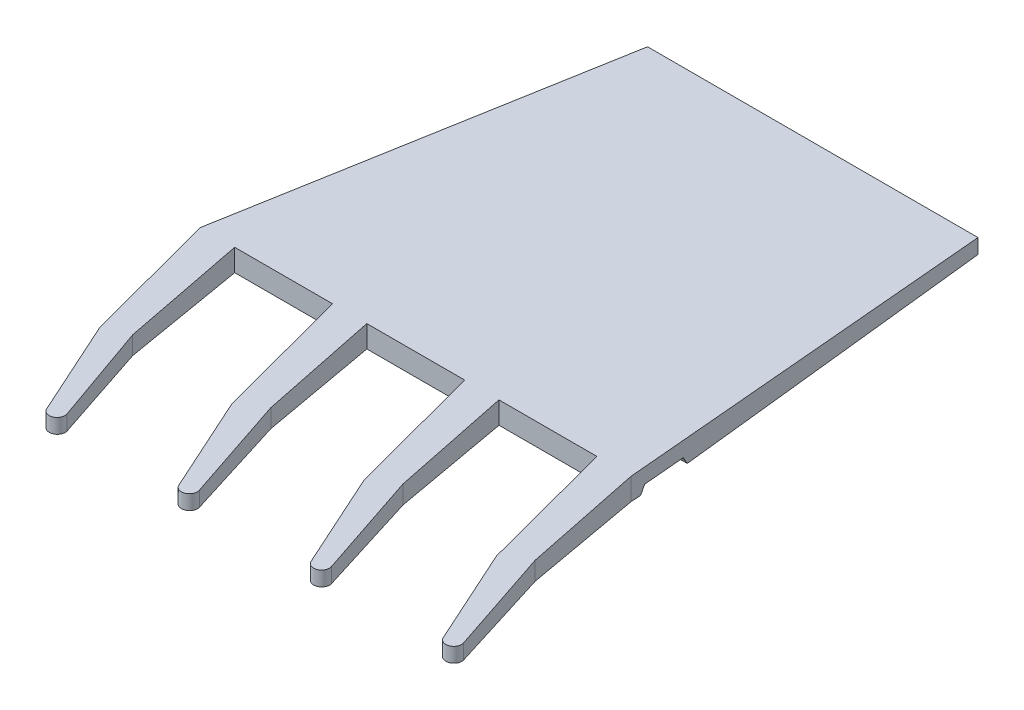
SolidWorks part; units mm, degrees
ref_plane "Front Plane" through (0, 0, 0) normal (0, 0, 1) x (1, 0, 0)
ref_plane "Top Plane" through (0, 0, 0) normal (0, 1, 0) x (1, 0, 0)
ref_plane "Right Plane" through (0, 0, 0) normal (1, 0, 0) x (0, 0, -1)
sketch "Sketch1" plane through (0, 0, 0) normal (0, 1, 0) x (1, 0, 0)
  line L0 (-32.5781, 0) -> (72.7976, 0) construction
  line L5 (0, 0) -> (0, 68.3726) construction
  line L27 (72.7976, -27.2489) -> (65.0609, -10.928) construction
  line L30 (-32.5781, 8.3167) -> (-32.5781, -27.2489) construction
  line L54 (-28, 8.3167) -> (-32.5781, 8.3167) construction
  line L60 (0, 68.3726) -> (0, -57.1527) construction
  line L62 (-32.5781, 68.3726) -> (72.7976, 68.3726) construction
  line L63 (-32.5781, 68.3726) -> (-32.5781, -57.1527) construction
  line L64 (-32.5781, -57.1527) -> (72.7976, -57.1527) construction
  line L65 (72.7976, 68.3726) -> (72.7976, -57.1527) construction
sketch "Sketch2" plane through (0, 0, 0) normal (1, 0, 0) x (0, 0, -1)
  line L0 (3.2707, -4.5742) -> (68.4088, -3.0014) construction
  line L1 (68.3726, 0) -> (68.4088, -3.0014) construction
  line L2 (68.3726, 0) -> (-57.1527, 0) construction
  line L7 (-7.1582, -4.5614) -> (-57.1563, -3) construction
  line L8 (-7.1582, -4.5614) -> (-6.2716, -3.0624) construction
  line L9 (2.3877, -3.0731) -> (-6.2716, -3.0624) construction
  line L10 (2.3877, -3.0731) -> (3.2707, -4.5742) construction
  line L11 (3.2707, -4.5742) -> (68.4088, -3.0014)
  line L12 (68.3726, 0) -> (68.4088, -3.0014)
  line L13 (68.3726, 0) -> (-58.6236, 0)
  line L14 (-58.6236, 0) -> (-58.6236, -2.9542)
  line L18 (-7.1582, -4.5614) -> (-58.6236, -2.9542)
  line L19 (-7.1582, -4.5614) -> (-6.2716, -3.0624)
  line L20 (2.3877, -3.0731) -> (-6.2716, -3.0624)
  line L21 (2.3877, -3.0731) -> (3.2707, -4.5742)
  line L22 (66.8718, -1.519) -> (-57.1545, -1.5) construction
  line L23 (66.8718, -1.519) -> (-58.6236, -1.4998) construction
extrude "Boss-Extrude1" add sketch "Sketch2" along normal up to vertex (72.7976 mm away) from vertex up to point (72.7976, 0, 57.1527) starting at point (-32.5781, 0, 57.1527)
sketch "Sketch3" plane through (0, 0, 0) normal (0, 1, 0) x (1, 0, 0)
  line L0 (-28, -9.2814) -> (-20.6376, -37.1687) construction
  line L1 (-20.6376, -37.1687) -> (-10.9213, -58.6236) construction
  line L2 (-10.9213, -58.6236) -> (-8.2024, -57.1527) construction
  line L3 (-8.2024, -57.1527) -> (-15.9391, -35.1847) construction
  line L4 (-15.9391, -35.1847) -> (-21, -9.2814) construction
  line L5 (-21, -9.2814) -> (-1, -9.2814) construction
  line L6 (-1, -9.2814) -> (6.3624, -37.1687) construction
  line L7 (6.3624, -37.1687) -> (16.0787, -58.6236) construction
  line L8 (16.0787, -58.6236) -> (18.7976, -57.1527) construction
  line L9 (18.7976, -57.1527) -> (11.0609, -33.9525) construction
  line L10 (11.0609, -33.9525) -> (6, -9.2814) construction
  line L11 (26, -9.2814) -> (6, -9.2814) construction
  line L12 (26, -9.2814) -> (33.3624, -37.1687) construction
  line L13 (33.3624, -37.1687) -> (43.0787, -58.6236) construction
  line L14 (43.0787, -58.6236) -> (45.7976, -57.1527) construction
  line L15 (45.7976, -57.1527) -> (38.0609, -33.9525) construction
  line L16 (38.0609, -33.9525) -> (33, -9.2814) construction
  line L17 (33, -9.2814) -> (53, -9.2814) construction
  line L18 (53, -9.2814) -> (60.3624, -37.1687) construction
  line L19 (60.3624, -37.1687) -> (70.0787, -58.6236) construction
  line L20 (70.0787, -58.6236) -> (72.7976, -57.1527) construction
  line L21 (72.7976, -57.1527) -> (65.0609, -33.9525) construction
  line L22 (65.0609, -33.9525) -> (60, -9.2814) construction
  line L23 (-28, -9.2814) -> (-20.6376, -37.1687)
  line L24 (-20.6376, -37.1687) -> (-10.9213, -58.6236) construction
  line L25 (-10.9213, -58.6236) -> (-8.2024, -57.1527) construction
  line L26 (-8.2024, -57.1527) -> (-15.9391, -35.1847) construction
  line L27 (-15.9391, -35.1847) -> (-21, -9.2814)
  line L28 (-21, -9.2814) -> (-1, -9.2814)
  line L29 (-1, -9.2814) -> (6.3624, -37.1687)
  line L30 (6.3624, -37.1687) -> (16.0787, -58.6236) construction
  line L31 (16.0787, -58.6236) -> (18.7976, -57.1527) construction
  line L32 (18.7976, -57.1527) -> (11.0609, -33.9525) construction
  line L33 (11.0609, -33.9525) -> (6, -9.2814)
  line L34 (26, -9.2814) -> (6, -9.2814)
  line L35 (26, -9.2814) -> (33.3624, -37.1687)
  line L36 (33.3624, -37.1687) -> (43.0787, -58.6236) construction
  line L37 (43.0787, -58.6236) -> (45.7976, -57.1527) construction
  line L38 (45.7976, -57.1527) -> (38.0609, -33.9525) construction
  line L39 (38.0609, -33.9525) -> (33, -9.2814)
  line L40 (33, -9.2814) -> (53, -9.2814)
  line L41 (53, -9.2814) -> (60.3624, -37.1687)
  line L42 (60.3624, -37.1687) -> (70.0787, -58.6236) construction
  line L43 (70.0787, -58.6236) -> (72.7976, -57.1527) construction
  line L44 (72.7976, -57.1527) -> (65.0609, -33.9525) construction
  line L45 (65.0609, -33.9525) -> (60, -9.2814)
  line L46 (-28, -9.2814) -> (-14.3075, 68.3726)
  line L47 (-14.3075, 68.3726) -> (53.2062, 68.3726)
  line L48 (53.2062, 68.3726) -> (60, -9.2814)
  line L49 (-32.5781, 68.3726) -> (72.7976, 68.3726) construction
  line L50 (-11.6316, -57.0553) -> (-20.6376, -37.1687)
  line L51 (-15.9391, -35.1847) -> (-8.6574, -55.8607)
  line L52 (15.3631, -57.0435) -> (6.3624, -37.1687)
  line L53 (11.0609, -33.9525) -> (18.3684, -55.8656)
  line L54 (33.3624, -37.1687) -> (42.3631, -57.0435)
  line L55 (45.3684, -55.8656) -> (38.0609, -33.9525)
  line L56 (60.3624, -37.1687) -> (69.3631, -57.0435)
  line L57 (72.3684, -55.8656) -> (65.0609, -33.9525)
  arc A0 (72.3684, -55.8656) -> (69.3631, -57.0435) centre (70.8353, -56.3768) cw
  arc A1 (45.3684, -55.8656) -> (42.3631, -57.0435) centre (43.8353, -56.3768) cw
  arc A2 (18.3684, -55.8656) -> (15.3631, -57.0435) centre (16.8353, -56.3768) cw
  arc A3 (-8.6574, -55.8607) -> (-11.6316, -57.0553) centre (-10.1704, -56.3936) cw
  dimension "D1" = 100
  dimension "D2" = 95
extrude "Cut-Extrude1" cut sketch "Sketch3" against normal through all flip side to cut
